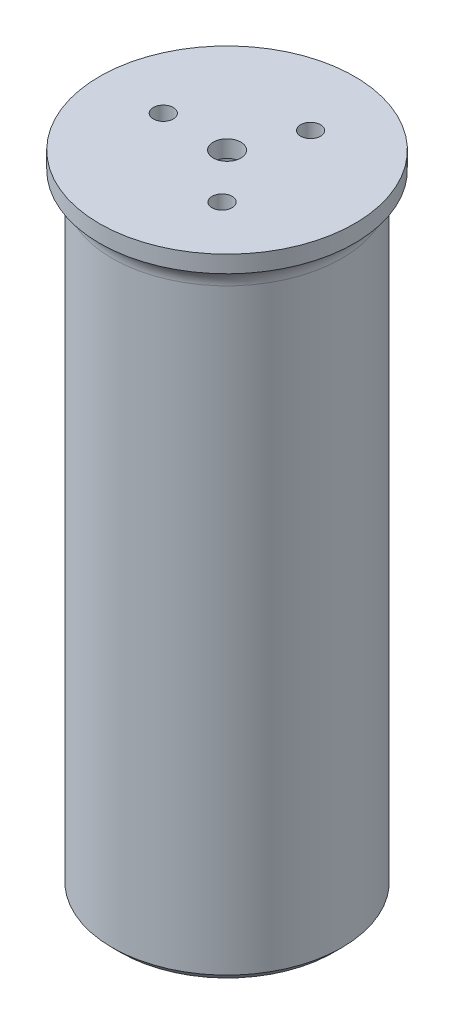
SolidWorks part; units mm, degrees
ref_plane "Front Plane" through (0, 0, 0) normal (0, 0, 1) x (1, 0, 0)
ref_plane "Top Plane" through (0, 0, 0) normal (0, 1, 0) x (1, 0, 0)
ref_plane "Right Plane" through (0, 0, 0) normal (1, 0, 0) x (0, 0, -1)
sketch "Sketch1" plane through (0, 0, 0) normal (0, 1, 0) x (1, 0, 0)
  circle A0 centre (0, 0) radius 30
  circle A1 centre (-15, -0.001) radius 2.35
  circle A2 centre (5.8324, 13.8197) radius 2.35
  circle A3 centre (10, -11.1803) radius 2.35
  dimension "D1" = 4.7
  dimension "D2" = 4.7
  dimension "D3" = 4.7
  dimension "D4" = 60
  dimension "D5" = 15
  dimension "D7" = 15
  dimension "D8" = 25
  dimension "D9" = 25
  dimension "D10" = 25
  dimension "D6" = 15
extrude "Boss-Extrude1" add sketch "Sketch1" along normal blind 4
sketch "Sketch2" plane through (0, 4, 0) normal (0, 1, 0) x (1, 0, 0)
  circle A0 centre (0, 0) radius 3.25
  dimension "D1" = 6.5
extrude "Cut-Extrude1" cut sketch "Sketch2" against normal blind 4
sketch "Sketch3" plane through (0, 0, 0) normal (0, -1, 0) x (1, 0, 0)
  circle A0 centre (0, 0) radius 25
  circle A1 centre (0, 0) radius 27
  dimension "D1" = 50
  dimension "D2" = 2
extrude "Boss-Extrude2" add sketch "Sketch3" along normal blind 150
chamfer "Chamfer1" distance 5 angle 45 1 edges at (0, -150, -27)
fillet "Fillet1" radius 5 1 edges at (0, 0, 27)
